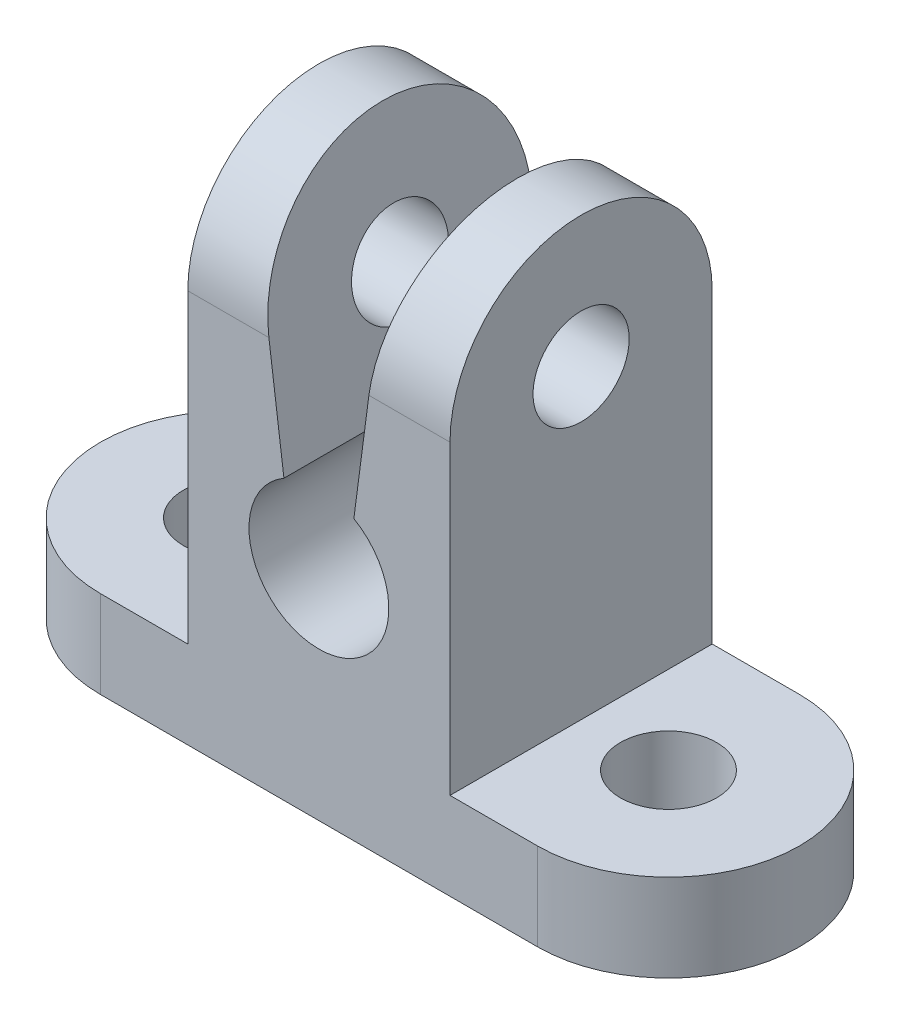
SolidWorks part; units mm, degrees
ref_plane "前视基准面" through (0, 0, 0) normal (0, 0, 1) x (1, 0, 0)
ref_plane "上视基准面" through (0, 0, 0) normal (0, 1, 0) x (1, 0, 0)
ref_plane "右视基准面" through (0, 0, 0) normal (1, 0, 0) x (0, 0, -1)
sketch "草图1" plane through (0, 0, 0) normal (0, 1, 0) x (1, 0, 0)
  line L0 (-5, 0) -> (5, 0) construction
  line L1 (-5, 3) -> (5, 3)
  line L2 (-5, -3) -> (5, -3)
  arc A0 (-5, 3) -> (-5, -3) centre (-5, 0) ccw
  arc A1 (5, -3) -> (5, 3) centre (5, 0) ccw
  point P2 (0, 0)
  dimension "D1" = 6
  dimension "D2" = 10
extrude "凸台-拉伸1" add sketch "草图1" along normal blind 2
sketch "草图2" plane through (0, 0, 0) normal (1, 0, 0) x (0, 0, -1)
  line L5 (-3, 0) -> (3, 0)
  line L6 (-3, 0) -> (-3, 12)
  line L7 (-3, 12) -> (3, 12)
  line L8 (3, 0) -> (3, 12)
  dimension "D1" = 12
  dimension "D2" = 6
extrude "凸台-拉伸2" add sketch "草图2" along normal mid plane 6
fillet "圆角1" 2 edges at (0, 12, -3) (0, 12, 3) type full round first side face at (0, 4, -3) second side face at (0, 4, 3) middle face at (0, 12, 0)
sketch "草图3" plane through (0, 0, -3) normal (0, 0, -1) x (-1, 0, 0)
  line L0 (0, 0) -> (0, 5) construction
  line L1 (-5, 0) -> (5, 0) construction
  line L2 (-0.8, 6.3856) -> (-1.7488, 13.5927)
  line L3 (-1.7488, 13.5927) -> (0.7841, 13.5927)
  line L4 (1.7488, 13.5927) -> (-0.7841, 13.5927)
  line L5 (0.8, 6.3856) -> (1.7488, 13.5927)
  circle A0 centre (0, 5) radius 1.6
  line M5 (3, 9) -> (-3, 9)
  dimension "D1" = 3.2
  dimension "D2" = 5
  dimension "D3" = 1.6
  dimension "D4" = 15
extrude "切除-拉伸1" cut sketch "草图3" against normal blind 28 contours A0 | L5 L4 L3 L2 M5 | A0 L5 L2 M5 region at (0, 7.832, -3) region at (0, 5, -3) region at (0, 11.4563, -3)
sketch "草图4" plane through (3, 0, 0) normal (1, 0, 0) x (0, 0, -1)
  circle A0 centre (0, 9) radius 1.1
  dimension "D1" = 2.2
extrude "切除-拉伸2" cut sketch "草图4" against normal blind 28
sketch "草图7" plane through (0, 2, 0) normal (0, 1, 0) x (1, 0, 0)
  circle A0 centre (5, 0) radius 1.1
  circle A1 centre (-5, 0) radius 1.1
  dimension "D1" = 2.2
  dimension "D2" = 2.2
extrude "切除-拉伸5" cut sketch "草图7" against normal blind 3.5
sketch "草图9" plane through (0, 0, 0) normal (0, -1, 0) x (1, 0, 0)
  circle A0 centre (0, 0) radius 1.5
  dimension "D1" = 3
extrude "切除-拉伸7" cut sketch "草图9" against normal blind 0.1
